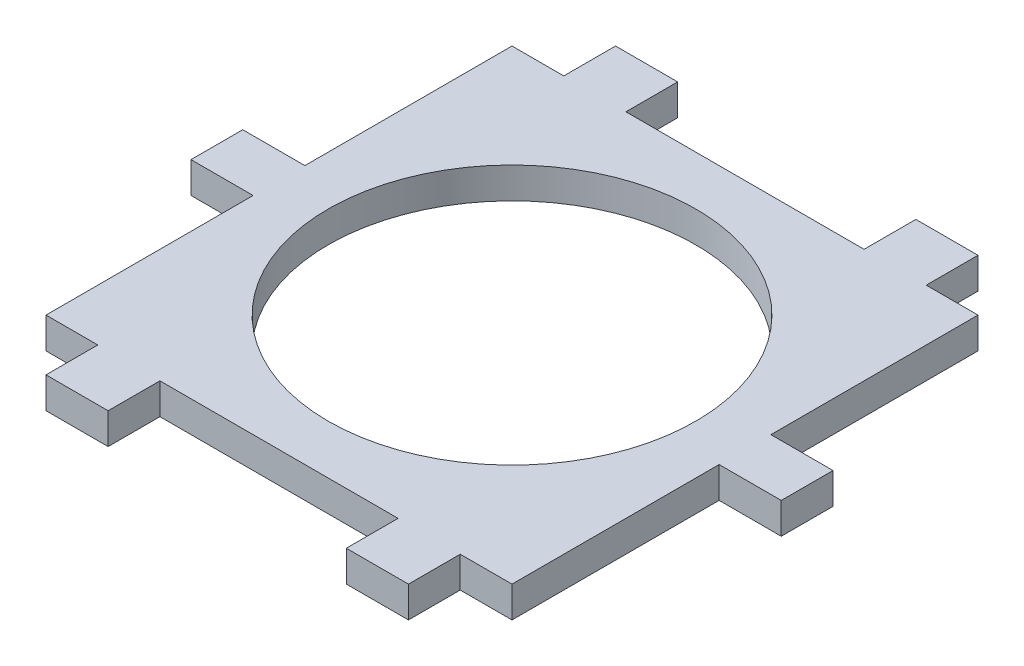
SolidWorks part; units mm, degrees
ref_plane "Alzado" through (0, 0, 0) normal (0, 0, 1) x (1, 0, 0)
ref_plane "Planta" through (0, 0, 0) normal (0, 1, 0) x (1, 0, 0)
ref_plane "Vista lateral" through (0, 0, 0) normal (1, 0, 0) x (0, 0, -1)
sketch "Croquis1" plane through (0, 0, 0) normal (0, 1, 0) x (1, 0, 0)
  line L1 (-22.5, 22.5) -> (22.5, 22.5)
  line L2 (-22.5, 22.5) -> (-22.5, -22.5)
  line L3 (-22.5, -22.5) -> (22.5, -22.5)
  line L4 (22.5, 22.5) -> (22.5, -22.5)
  line L5 (-22.5, 22.5) -> (22.5, -22.5) construction
  line L6 (-22.5, -22.5) -> (22.5, 22.5) construction
  line L7 (-17.5, 22.5) -> (-11.5, 22.5)
  line L8 (-17.5, 22.5) -> (-17.5, 27.5)
  line L9 (-17.5, 27.5) -> (-11.5, 27.5)
  line L10 (-11.5, 22.5) -> (-11.5, 27.5)
  line L11 (11.5, 22.5) -> (17.5, 22.5)
  line L12 (11.5, 22.5) -> (11.5, 27.5)
  line L13 (11.5, 27.5) -> (17.5, 27.5)
  line L14 (17.5, 22.5) -> (17.5, 27.5)
  line L15 (-17.5, -22.5) -> (-11.5, -22.5)
  line L16 (-17.5, -22.5) -> (-17.5, -27.5)
  line L17 (-17.5, -27.5) -> (-11.5, -27.5)
  line L18 (-11.5, -22.5) -> (-11.5, -27.5)
  line L19 (11.5, -22.5) -> (17.5, -22.5)
  line L20 (11.5, -22.5) -> (11.5, -27.5)
  line L21 (11.5, -27.5) -> (17.5, -27.5)
  line L22 (17.5, -22.5) -> (17.5, -27.5)
  line L23 (-22.5, 2.5) -> (-28.5, 2.5)
  line L24 (-22.5, 2.5) -> (-22.5, -2.5)
  line L25 (-22.5, -2.5) -> (-28.5, -2.5)
  line L26 (-28.5, 2.5) -> (-28.5, -2.5)
  line L27 (22.5, 2.5) -> (28.5, 2.5)
  line L28 (22.5, 2.5) -> (22.5, -2.5)
  line L29 (22.5, -2.5) -> (28.5, -2.5)
  line L30 (28.5, 2.5) -> (28.5, -2.5)
  circle A0 centre (0, 0) radius 17.75
  point P0 (0, 0)
  dimension "D13" = 35.5
  dimension "D1" = 45
  dimension "D2" = 45
  dimension "D3" = 6
  dimension "D4" = 6
  dimension "D5" = 5
  dimension "D6" = 5
  dimension "D7" = 5
  dimension "D8" = 5
  dimension "D9" = 6
  dimension "D10" = 6
  dimension "D11" = 5
  dimension "D12" = 5
  dimension "D14" = 5
  dimension "D15" = 6
  dimension "D16" = 5
  dimension "D17" = 6
  dimension "D18" = 20
  dimension "D19" = 20
extrude "Saliente-Extruir1" add sketch "Croquis1" along normal blind 3 contours L4 L1 L2 L3 A0 | L1 L10 L9 L8 | L1 L14 L13 L12 | L18 L3 L16 L17 | L22 L3 L20 L21 region at (-20, 0, -21.8636) region at (-14.5, 0, -25) region at (14.5, 0, -25) region at (-14.5, 0, 25) region at (14.5, 0, 25)
extrude "Saliente-Extruir2" add sketch "Croquis1<3>" along normal blind 3 contours L23 L26 L25 L2 | L30 L27 L4 L29 region at (-25.5, 0, 0) region at (25.5, 0, 0)
sketch "Croquis1<3>" plane through (0, 0, 0) normal (0, 1, 0) x (1, 0, 0) same geometry as "Croquis1"
